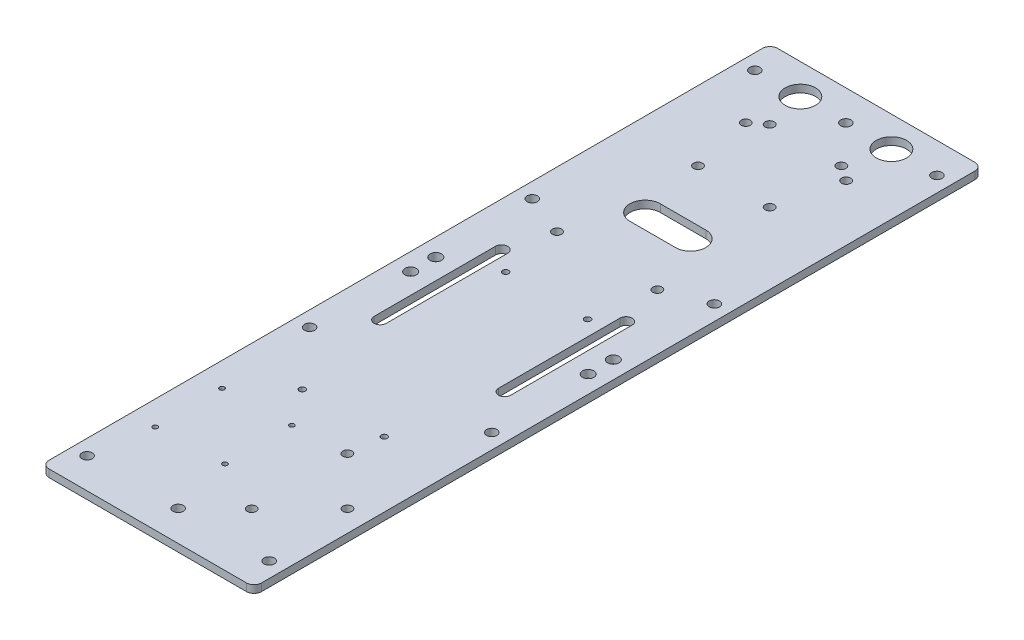
SolidWorks part; units mm, degrees
ref_plane "Front Plane" through (0, 0, 0) normal (0, 0, 1) x (1, 0, 0)
ref_plane "Top Plane" through (0, 0, 0) normal (0, 1, 0) x (1, 0, 0)
ref_plane "Right Plane" through (0, 0, 0) normal (1, 0, 0) x (0, 0, -1)
sketch "Sketch2" plane through (0, 0, 0) normal (0, 1, 0) x (1, 0, 0)
  line L0 (-44.45, 0) -> (44.45, 0) construction
  line L1 (-41.275, 152.4) -> (41.275, 152.4)
  line L2 (-44.45, 149.225) -> (-44.45, -149.225)
  line L3 (-41.275, -152.4) -> (41.275, -152.4)
  line L4 (44.45, 149.225) -> (44.45, -149.225)
  line L5 (0, 152.4) -> (0, -152.4) construction
  arc A0 (-44.45, -149.225) -> (-41.275, -152.4) centre (-41.275, -149.225) ccw
  arc A1 (41.275, -152.4) -> (44.45, -149.225) centre (41.275, -149.225) ccw
  arc A2 (41.275, 152.4) -> (44.45, 149.225) centre (41.275, 149.225) cw
  arc A3 (-41.275, 152.4) -> (-44.45, 149.225) centre (-41.275, 149.225) ccw
  point P8 (0, 0)
  point P13 (-44.45, -152.4)
  point P16 (44.45, -152.4)
  point P21 (-44.45, 152.4)
  dimension "D3" = 3.175
  dimension "D1" = 304.8
  dimension "D2" = 88.9
extrude "Plate Thickness" add sketch "Sketch2" along normal blind 3.175 contours L2 A0 L3 A1 L4 A2 L1 A3
sketch "Sketch3" plane through (0, 3.175, 0) normal (0, 1, 0) x (1, 0, 0)
  line L0 (-44.45, 149.225) -> (-44.45, -149.225) construction
  line L1 (-41.275, 152.4) -> (41.275, 152.4) construction
  line L4 (0, 152.4) -> (0, -152.4) construction
  line L5 (-41.275, -152.4) -> (41.275, -152.4) construction
  line L6 (-41.275, -152.4) -> (41.275, -152.4) construction
  circle A0 centre (-38.1, 139.7) radius 2.159
  circle A1 centre (-38.1, 46.5667) radius 2.159
  circle A2 centre (-38.1, -46.5667) radius 2.159
  circle A3 centre (-38.1, -139.7) radius 2.159
  circle A4 centre (38.1, -139.7) radius 2.159
  circle A5 centre (38.1, -46.5667) radius 2.159
  circle A6 centre (38.1, 46.5667) radius 2.159
  circle A7 centre (38.1, 139.7) radius 2.159
  circle A8 centre (0, 139.7) radius 2.159
  circle A9 centre (0, -139.7) radius 2.159
  dimension "D1" = 4.318
  dimension "D4" = 4.318
  dimension "D2" = 6.35
  dimension "D3" = 12.7
  dimension "D5" = 12.7
  dimension "D6" = 12.7
  dimension "D7" = 93.1333
  dimension "D8" = 93.1333
extrude "Mounting holes" cut sketch "Sketch3" against normal through all
sketch "Sketch4" plane through (0, 3.175, 0) normal (0, 1, 0) x (1, 0, 0)
  line L0 (-21.0058, 39.8143) -> (21.0058, 39.8143) construction
  line L1 (0, 0) -> (0, 139.7) construction
  circle A0 centre (-21.0058, 118.8083) radius 1.905
  circle A1 centre (-21.0058, 39.8143) radius 1.905
  circle A2 centre (21.0058, 39.8143) radius 1.905
  circle A3 centre (21.0058, 118.8083) radius 1.905
  point P13 (0, 39.8143)
  point P17 (0, 69.85)
  point P18 (0, 69.85)
  dimension "D1" = 3.81
  dimension "D2" = 78.994
  dimension "D3" = 42.0116
extrude "Jetson Holes (w/o mount)" cut sketch "Sketch4" against normal through all
sketch "Sketch5" plane through (0, 3.175, 0) normal (0, 1, 0) x (1, 0, 0)
  line L0 (-41.275, 152.4) -> (41.275, 152.4) construction
  line L1 (44.45, 149.225) -> (44.45, -149.225) construction
  circle A1 centre (-15.3784, 123.19) radius 1.905
  circle A3 centre (14.619, 123.19) radius 1.905
  circle A4 centre (14.619, 93.1926) radius 1.905
  circle A5 centre (-15.3784, 93.1926) radius 1.905
  dimension "D1" = 3.81
  dimension "D2" = 29.9974
  dimension "D4" = 29.21
  dimension "D5" = 29.831
  dimension "D3" = 29.9974
extrude "PDB holes" cut sketch "Sketch5" against normal through all
sketch "Sketch6" plane through (0, 3.175, 0) normal (0, 1, 0) x (1, 0, 0)
  line L0 (-41.275, -152.4) -> (41.275, -152.4) construction
  line L1 (44.45, 149.225) -> (44.45, -149.225) construction
  circle A6 centre (35.56, -104.394) radius 1.905
  circle A7 centre (15.56, -84.46) radius 1.905
  circle A8 centre (15.56, -124.46) radius 1.905
  point P2 (0, 0)
  dimension "D1" = 27.94
  dimension "D5" = 3.81
  dimension "D2" = 8.89
  dimension "D6" = 40
  dimension "D7" = 20
  dimension "D8" = 20.066
sketch "Sketch7" plane through (0, 3.175, 0) normal (0, 1, 0) x (1, 0, 0)
  line L0 (0, 152.4) -> (0, -152.4) construction
  line L1 (-41.275, 152.4) -> (41.275, 152.4) construction
  line L2 (-41.275, -152.4) -> (41.275, -152.4) construction
  line L3 (17.145, 14.4893) -> (-17.145, 14.4893) construction
  circle A0 centre (-17.145, 14.4893) radius 1.27
  circle A1 centre (-17.145, -70.6007) radius 1.27
  circle A2 centre (17.145, -70.6007) radius 1.27
  circle A3 centre (17.145, 14.4893) radius 1.27
  point P14 (0, 14.4893)
  dimension "D1" = 2.54
  dimension "D2" = 85.09
  dimension "D3" = 34.29
extrude "PixHawk Holes" cut sketch "Sketch7" against normal through all
sketch "Sketch8" plane through (0, 3.175, 0) normal (0, 1, 0) x (1, 0, 0)
  line L0 (0, 152.4) -> (0, -115.5095) construction
  line L1 (-41.275, 152.4) -> (41.275, 152.4) construction
  line L2 (-26.035, 21.6897) -> (-26.035, -29.1103) construction
  line L3 (-23.495, 21.6897) -> (-23.495, -29.1103)
  line L4 (-28.575, 21.6897) -> (-28.575, -29.1103)
  line L5 (26.035, 21.6897) -> (26.035, -29.1103) construction
  line L6 (23.495, 21.6897) -> (23.495, -29.1103)
  line L7 (28.575, 21.6897) -> (28.575, -29.1103)
  arc A0 (-23.495, 21.6897) -> (-28.575, 21.6897) centre (-26.035, 21.6897) ccw
  arc A1 (-28.575, -29.1103) -> (-23.495, -29.1103) centre (-26.035, -29.1103) ccw
  arc A2 (23.495, 21.6897) -> (28.575, 21.6897) centre (26.035, 21.6897) cw
  arc A3 (28.575, -29.1103) -> (23.495, -29.1103) centre (26.035, -29.1103) cw
  point P7 (-26.035, -3.7103)
  point P14 (26.035, -3.7103)
  dimension "D1" = 50.8
  dimension "D2" = 5.08
  dimension "D3" = 26.035
extrude "Battery Holes" cut sketch "Sketch8" against normal through all
sketch "Sketch9" plane through (0, 3.175, 0) normal (0, 1, 0) x (1, 0, 0)
  line L0 (44.45, 149.225) -> (44.45, -149.225) construction
  line L1 (-41.275, -152.4) -> (41.275, -152.4) construction
  circle A0 centre (6.8334, -85.3) radius 2
  circle A1 centre (34.3334, -85.3) radius 2
  circle A2 centre (34.3334, -114.3) radius 2
  circle A3 centre (6.8334, -114.3) radius 2
  dimension "D1" = 4
  dimension "D3" = 10.1166
  dimension "D5" = 38.1
  dimension "D2" = 27.5
  dimension "D4" = 29
sketch "Sketch10" plane through (0, 3.175, 0) normal (0, 1, 0) x (1, 0, 0)
  line L0 (-44.45, 149.225) -> (-44.45, -149.225) construction
  circle A0 centre (-34.3155, -87.0086) radius 1
  circle A1 centre (-34.29, -115.0086) radius 1
  circle A2 centre (-6.3166, -85.7891) radius 1
  circle A3 centre (-6.3166, -113.7891) radius 1
  dimension "D1" = 2
  dimension "D2" = 28
  dimension "D3" = 28
  dimension "D4" = 28
  dimension "D5" = 10.16
extrude "Ventral Camera holes" cut sketch "Sketch10" against normal up to next
sketch "Sketch12" plane through (0, 3.175, 0) normal (0, 1, 0) x (1, 0, 0)
  line L0 (-41.275, 152.4) -> (41.275, 152.4) construction
  circle A0 centre (-19.05, 139.7) radius 6.35
  circle A1 centre (19.05, 139.7) radius 6.35
  circle A2 centre (-38.1, 139.7) radius 2.159 construction
  dimension "D1" = 19.05
  dimension "D3" = 12.7
  dimension "D2" = 38.1
  dimension "D4" = 12.7
extrude "Wifi antenna holes" cut sketch "Sketch12" against normal through all
extrude "TeraRanger Holes" cut sketch "Sketch6" against normal through all
sketch "Sketch14" plane through (0, 3.175, 0) normal (0, 1, 0) x (1, 0, 0)
  line L0 (0, 0) -> (106.8092, 0) construction
  line L1 (106.8092, 0) -> (-134.4112, 0) construction
  line L2 (0, 0) -> (0, -162.7051) construction
  circle A0 centre (-37.138, 5.2462) radius 2.3812
  circle A1 centre (-37.138, -5.2462) radius 2.3812
  circle A2 centre (37.138, -5.2462) radius 2.3812
  circle A3 centre (37.138, 5.2462) radius 2.3812
  dimension "D1" = 10.4925
  dimension "D2" = 4.7625
extrude "Sonarholes" cut sketch "Sketch14" against normal through all
sketch "Sketch15" plane through (0, 0, 0) normal (0, -1, 0) x (-1, 0, 0)
  line L0 (-9.525, 65.2143) -> (9.525, 65.2143) construction
  line L1 (-9.525, 71.5643) -> (9.525, 71.5643)
  line L2 (-9.525, 58.8643) -> (9.525, 58.8643)
  line L4 (41.275, 152.4) -> (-41.275, 152.4) construction
  arc A0 (-9.525, 71.5643) -> (-9.525, 58.8643) centre (-9.525, 65.2143) ccw
  arc A1 (9.525, 58.8643) -> (9.525, 71.5643) centre (9.525, 65.2143) ccw
  circle A3 centre (-21.0058, 39.8143) radius 1.905 construction
  point P2 (0, 65.2143)
  point P9 (0, 0)
  point P10 (0, 152.4)
  dimension "D1" = 25.4
  dimension "D2" = 19.05
  dimension "D3" = 12.7
extrude "Cut-Extrude1" cut sketch "Sketch15" against normal through all
